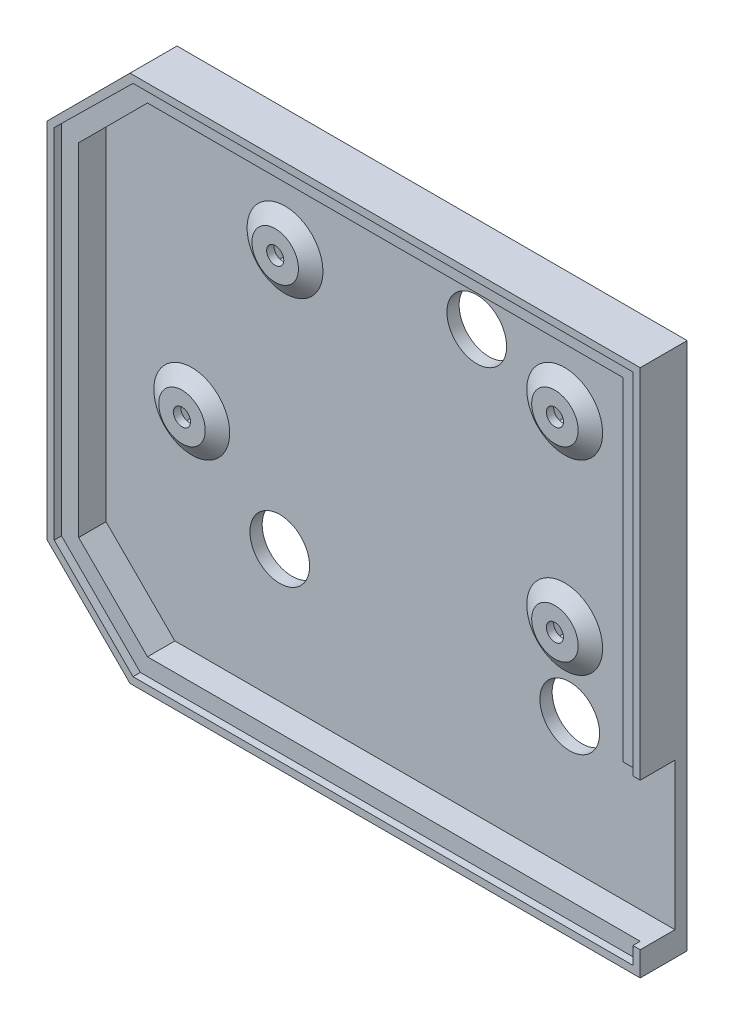
SolidWorks part; units mm, degrees
ref_plane "Plan de face" through (0, 0, 0) normal (0, 0, 1) x (1, 0, 0)
ref_plane "Plan de dessus" through (0, 0, 0) normal (0, 1, 0) x (1, 0, 0)
ref_plane "Plan de droite" through (0, 0, 0) normal (1, 0, 0) x (0, 0, -1)
sketch "Esquisse1" plane through (0, 0, 0) normal (0, 0, 1) x (1, 0, 0)
  line L0 (0, -85) -> (17, -102)
  line L4 (121.25, 6) -> (121.25, -102)
  line L5 (17, 6) -> (0, -11)
  line L7 (121.25, 6) -> (17, 6)
  line L8 (0, -11) -> (0, -85)
  line L9 (17, -102) -> (121.25, -102)
  dimension "D1" = 108
  dimension "D2" = 121.25
  dimension "D3" = 17
  dimension "D4" = 17
  dimension "D5" = 17
  dimension "D6" = 17
extrude "Boss.-Extru.1" add sketch "Esquisse1" along normal blind 2.5
sketch "Esquisse2" plane through (0, 0, 2.5) normal (0, 0, 1) x (1, 0, 0)
  line L0 (0, -11) -> (0, -85) construction
  line L1 (5, 1) -> (116.25, 1) construction
  line L2 (5, 1) -> (5, -97) construction
  line L3 (5, -97) -> (116.25, -97) construction
  line L4 (116.25, 1) -> (116.25, -97) construction
  line L5 (17, -102) -> (121.25, -102) construction
  line L6 (121.25, -102) -> (121.25, 6) construction
  line L7 (121.25, 6) -> (17, 6) construction
  line L9 (5, -82.9289) -> (19.0711, -97)
  line L10 (0, -85) -> (17, -102) construction
  line L11 (5, -13.0711) -> (19.0711, 1)
  line L12 (17, 6) -> (0, -11) construction
  line L13 (116.25, 1) -> (19.0711, 1)
  line L14 (5, -13.0711) -> (5, -82.9289)
  line L15 (19.0711, -97) -> (116.25, -97)
  line L16 (121.25, 6) -> (121.25, -102) construction
  line L17 (121.25, -102) -> (17, -102)
  line L18 (17, -102) -> (0, -85)
  line L19 (0, -85) -> (0, -11)
  line L20 (0, -11) -> (17, 6)
  line L21 (17, 6) -> (121.25, 6)
  line L30 (121.25, -2.5) -> (121.25, 6)
  line L31 (116.25, -97) -> (121.25, -97)
  line L32 (121.25, -97) -> (121.25, -102)
  line L33 (116.25, 1) -> (116.25, -67)
  line L34 (116.25, -67) -> (121.25, -67)
  line L35 (121.25, -67) -> (121.25, -2.5)
  point P24 (118.75, -97)
  dimension "D1" = 5
  dimension "D2" = 5
  dimension "D3" = 5
  dimension "D4" = 5
  dimension "D5" = 5
  dimension "D6" = 5
  dimension "D7" = 30
extrude "Boss.-Extru.2" add sketch "Esquisse2" along normal blind 7.1
sketch "Esquisse3" plane through (0, 0, 2.5) normal (0, 0, 1) x (1, 0, 0)
  line L0 (121.25, -97) -> (19.0711, -97) construction
  line L1 (19.0711, 1) -> (116.25, 1) construction
  line L2 (116.25, 1) -> (116.25, -67) construction
  line L3 (5, -82.9289) -> (5, -13.0711) construction
  circle A0 centre (99.75, -70) radius 6.1
  circle A1 centre (80.75, -11) radius 6.1
  circle A2 centre (40.5, -70) radius 6.1
  dimension "D1" = 27
  dimension "D2" = 27
  dimension "D3" = 12
  dimension "D4" = 16.5
  dimension "D5" = 35.5
  dimension "D6" = 35.5
extrude "Enlèv. mat.-Extru.1" cut sketch "Esquisse3" against normal blind 10
sketch "Esquisse4" plane through (0, 0, 2.5) normal (0, 0, 1) x (1, 0, 0)
  line L0 (116.25, 1) -> (116.25, -67) construction
  line L1 (19.0711, 1) -> (116.25, 1) construction
  point P0 (41.57, -16.53)
  point P1 (22.52, -54.63)
  point P2 (98.72, -54.63)
  point P3 (98.72, -16.53)
  dimension "D1" = 17.53
  dimension "D2" = 17.53
  dimension "D3" = 38.1
  dimension "D4" = 57.15
  dimension "D5" = 76.2
ref_axis "Axe1" through (98.72, -54.63, 2.5) along (0, 0, 1)
ref_axis "Axe2" through (22.52, -54.63, 2.5) along (0, 0, 1)
ref_axis "Axe3" through (41.57, -16.53, 2.5) along (0, 0, 1)
ref_axis "Axe4" through (98.72, -16.53, 2.5) along (0, 0, 1)
ref_plane "Plan1" through (0, -54.63, 0) normal (0, -1, 0) x (-1, 0, 0)
ref_plane "Plan2" through (0, -16.53, 0) normal (0, 1, 0) x (1, 0, 0)
sketch "Esquisse9" plane through (0, -54.63, 0) normal (0, -1, 0) x (-1, 0, 0)
  line L0 (-96.97, -2.5) -> (-90.97, -2.5)
  line L1 (-90.97, -2.5) -> (-93.97, -4.5)
  line L2 (-93.97, -4.5) -> (-96.97, -4.5)
  line L3 (-96.97, -4.5) -> (-96.97, -2.5)
  line L4 (-98.72, -2.5) -> (-98.72, -52.6753) construction
  point P0 (-98.5795, 0)
  dimension "D1" = 2
  dimension "D2" = 1.75
  dimension "D3" = 3
  dimension "D4" = 6
ref_point "Point1"
ref_point "Point2"
ref_point "Point3"
ref_point "Point4"
revolve "Révolution1" add sketch "Esquisse9" angle 360 about axis through (98.72, -54.63, 2.5) along (0, 0, 1)
sketch "Esquisse11" plane through (0, -54.63, 0) normal (0, -1, 0) x (-1, 0, 0)
  line L0 (-24.27, -2.5) -> (-30.27, -2.5)
  line L1 (-30.27, -2.5) -> (-27.27, -4.5)
  line L2 (-27.27, -4.5) -> (-24.27, -4.5)
  line L3 (-24.27, -4.5) -> (-24.27, -2.5)
  line L4 (-22.52, -2.5) -> (-22.52, -52.6753) construction
  dimension "D1" = 1.75
  dimension "D2" = 3
  dimension "D3" = 6
  dimension "D4" = 2
revolve "Révolution2" add sketch "Esquisse11" angle 360 about axis through (22.52, -54.63, 2.5) along (0, 0, 1)
sketch "Esquisse12" plane through (0, -16.53, 0) normal (0, 1, 0) x (1, 0, 0)
  line L0 (96.97, -2.5) -> (90.97, -2.5)
  line L1 (90.97, -2.5) -> (93.97, -4.5)
  line L2 (93.97, -4.5) -> (96.97, -4.5)
  line L3 (96.97, -4.5) -> (96.97, -2.5)
  line L4 (98.72, -2.5) -> (98.72, -52.6753) construction
  dimension "D1" = 1.75
  dimension "D2" = 2
  dimension "D3" = 3
  dimension "D4" = 6
revolve "Révolution3" add sketch "Esquisse12" angle 360 about axis through (98.72, -16.53, 2.5) along (0, 0, 1)
sketch "Esquisse13" plane through (0, -16.53, 0) normal (0, 1, 0) x (1, 0, 0)
  line L0 (43.32, -2.5) -> (49.32, -2.5)
  line L1 (49.32, -2.5) -> (46.32, -4.5)
  line L2 (46.32, -4.5) -> (43.32, -4.5)
  line L3 (43.32, -4.5) -> (43.32, -2.5)
  line L4 (41.57, -2.5) -> (41.57, -52.6753) construction
  dimension "D1" = 1.75
  dimension "D2" = 3
  dimension "D3" = 6
  dimension "D4" = 2
revolve "Révolution4" add sketch "Esquisse13" angle 360 about axis through (41.57, -16.53, 2.5) along (0, 0, 1)
hole_wizard "Dégagement M31" positions "Esquisse14" profile "Esquisse15" hole size "M3" standard "Ansi Metric" end condition up to next
sketch "Esquisse14" plane through (0, 0, 2.5) normal (0, 0, 1) x (1, 0, 0)
  point P0 (98.72, -54.63)
  point P3 (22.52, -54.63)
  point P6 (98.72, -16.53)
  point P9 (41.57, -16.53)
sketch "Esquisse15" plane through (98.72, -54.63, 2.5) normal (1, 0, 0) x (0, -1, 0)
  line L0 (0, 0) -> (0, 2.5)
  line L1 (0, 2.5) -> (1.8, 2.5)
  line L2 (1.8, 2.5) -> (1.8, 0)
  line L5 (1.8, 0) -> (0, 0)
  line L11 (0, -6.35) -> (0, 107.95) construction
  dimension "Diamètre du perçage jusqu'au prochain" = 3.6
  dimension "Profondeur du perçage jusqu'au prochain" = 2.5
ref_point "Point5"
ref_point "Point6"
ref_point "Point7"
ref_point "Point8"
sketch "Esquisse16" plane through (0, 0, 0) normal (0, 0, -1) x (-1, 0, 0)
  line L0 (-121.25, 6) -> (-17, 6) construction
  line L1 (-24.0788, -51.93) -> (-25.6377, -54.63)
  line L2 (-25.6377, -54.63) -> (-24.0788, -57.33)
  line L3 (-24.0788, -57.33) -> (-20.9612, -57.33)
  line L4 (-20.9612, -57.33) -> (-19.4023, -54.63)
  line L5 (-19.4023, -54.63) -> (-20.9612, -51.93)
  line L6 (-20.9612, -51.93) -> (-24.0788, -51.93)
  line L7 (-100.2788, -51.93) -> (-101.8377, -54.63)
  line L8 (-101.8377, -54.63) -> (-100.2788, -57.33)
  line L9 (-100.2788, -57.33) -> (-97.1612, -57.33)
  line L10 (-97.1612, -57.33) -> (-95.6023, -54.63)
  line L11 (-95.6023, -54.63) -> (-97.1612, -51.93)
  line L12 (-97.1612, -51.93) -> (-100.2788, -51.93)
  line L13 (-100.2788, -13.83) -> (-101.8377, -16.53)
  line L14 (-101.8377, -16.53) -> (-100.2788, -19.23)
  line L15 (-100.2788, -19.23) -> (-97.1612, -19.23)
  line L16 (-97.1612, -19.23) -> (-95.6023, -16.53)
  line L17 (-95.6023, -16.53) -> (-97.1612, -13.83)
  line L18 (-97.1612, -13.83) -> (-100.2788, -13.83)
  line L19 (-43.1288, -13.83) -> (-44.6877, -16.53)
  line L20 (-44.6877, -16.53) -> (-43.1288, -19.23)
  line L21 (-43.1288, -19.23) -> (-40.0112, -19.23)
  line L22 (-40.0112, -19.23) -> (-38.4523, -16.53)
  line L23 (-38.4523, -16.53) -> (-40.0112, -13.83)
  line L24 (-40.0112, -13.83) -> (-43.1288, -13.83)
  circle A0 centre (-22.52, -54.63) radius 2.7 construction
  circle A1 centre (-98.72, -54.63) radius 2.7 construction
  circle A2 centre (-98.72, -16.53) radius 2.7 construction
  circle A3 centre (-41.57, -16.53) radius 2.7 construction
  dimension "D1" = 5.4
  dimension "D2" = 5.4
  dimension "D3" = 5.4
  dimension "D4" = 5.4
extrude "Enlèv. mat.-Extru.2" cut sketch "Esquisse16" against normal blind 3
sketch "Esquisse17" plane through (0, 0, 9.6) normal (0, 0, 1) x (1, 0, 0)
  line L0 (17, -102) -> (121.25, -102) construction
  line L1 (119.75, -100.5) -> (1.5, -100.5) construction
  line L2 (119.75, -100.5) -> (119.75, 4.5)
  line L3 (119.75, 4.5) -> (1.5, 4.5) construction
  line L4 (1.5, -100.5) -> (1.5, 4.5) construction
  line L5 (121.25, -102) -> (121.25, -97) construction
  line L6 (0, -11) -> (0, -85) construction
  line L7 (121.25, 6) -> (17, 6) construction
  line L8 (19.0711, -97) -> (17, -102) construction
  line L9 (5, -82.9289) -> (0, -85) construction
  line L10 (5, -13.0711) -> (0, -11) construction
  line L11 (19.0711, 1) -> (17, 6) construction
  line L12 (119.75, 4.5) -> (116.25, 1) construction
  line L13 (119.75, -100.5) -> (17.6213, -100.5)
  line L14 (17.6213, -100.5) -> (1.5, -84.3787)
  line L15 (1.5, -84.3787) -> (1.5, -11.3877)
  line L16 (1.5, -11.3877) -> (17.6213, 4.5)
  line L17 (17.6213, 4.5) -> (119.75, 4.5)
  dimension "D1" = 1.5
  dimension "D2" = 1.5
  dimension "D3" = 1.5
  dimension "D4" = 1.5
extrude "Enlèv. mat.-Extru.3" cut sketch "Esquisse17" against normal blind 1.5
